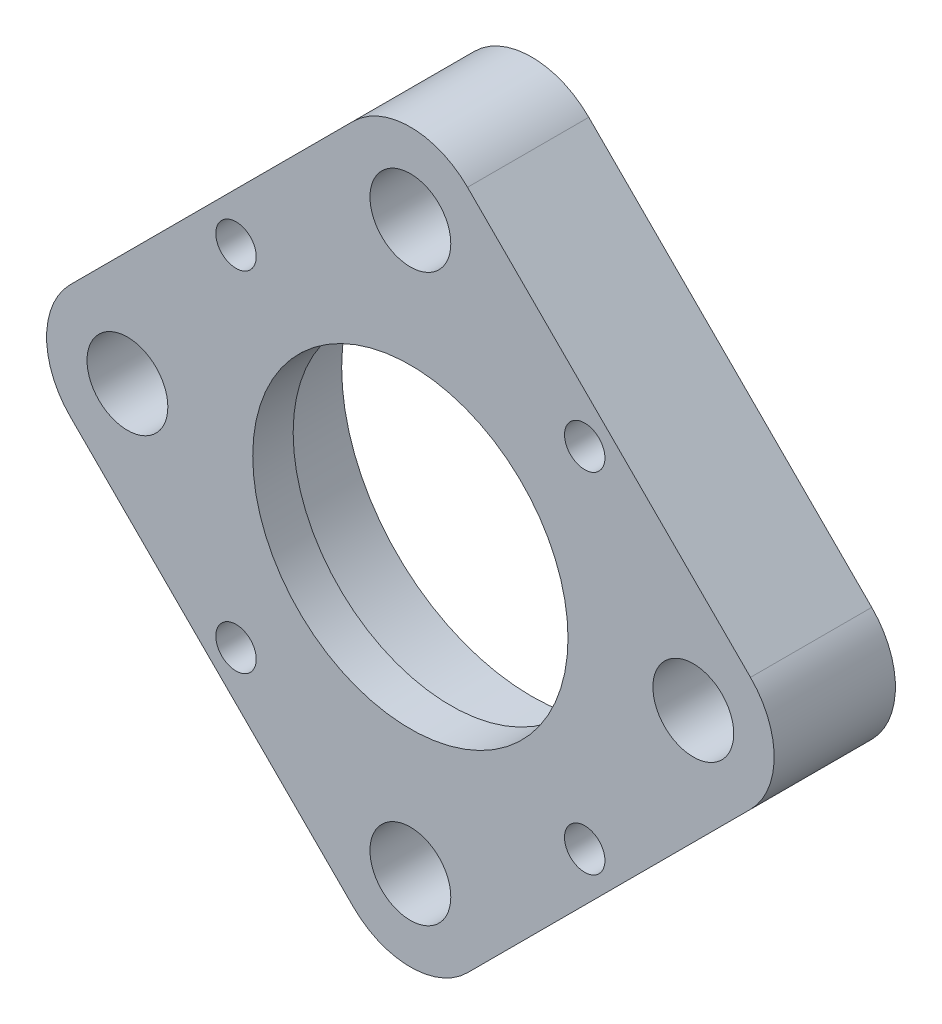
SolidWorks part; units mm, degrees
material "Stop 1060"
ref_plane "Płaszczyzna przednia" through (0, 0, 0) normal (0, 0, 1) x (1, 0, 0)
ref_plane "Płaszczyzna górna" through (0, 0, 0) normal (0, 1, 0) x (1, 0, 0)
ref_plane "Płaszczyzna prawa" through (0, 0, 0) normal (1, 0, 0) x (0, 0, -1)
sketch "Szkic1" plane through (0, 0, 0) normal (0, 0, 1) x (1, 0, 0)
  circle A0 centre (0, 0) radius 23.5
  circle A1 centre (0, 0) radius 19.5
  circle A2 centre (0, 0) radius 35
  dimension "D1" = 39
  dimension "D2" = 47
extrude "Dodanie-wyciągnięcie3" add sketch "Szkic1" along normal blind 5 contours A2 A0 | A0 A1 region at (-22.8353, 0, 0) region at (-34.0101, 0, 0)
sketch "Szkic4" plane through (0, 0, 0) normal (0, 0, -1) x (-1, 0, 0)
  circle A0 centre (0, 0) radius 23.5
  circle A1 centre (0, 0) radius 35
  circle M2 centre (0, 0) radius 35
  dimension "D1" = 47
extrude "Dodanie-wyciągnięcie5" add sketch "Szkic4" along normal blind 10 contours A0 M2 region at (34.0101, 0, 0)
sketch "Szkic10" plane through (0, 0, -10) normal (0, 0, -1) x (-1, 0, 0)
  circle A0 centre (0, 0) radius 30.5
  point P5 (-30.5, 0)
  point P6 (30.5, 0)
sketch "Szkic13" plane through (0, 0, -10) normal (0, 0, -1) x (-1, 0, 0)
  circle A0 centre (0, 35) radius 6
  circle A1 centre (0, 35) radius 10
  circle A3 centre (0, 0) radius 35
  circle A4 centre (0, -35) radius 6
  circle A5 centre (0, -35) radius 10
  circle A6 centre (-35, 0) radius 10
  circle A7 centre (35, 0) radius 10
  point P18 (-35, 0)
  point P20 (35, 0)
  circle M7 centre (0, 0) radius 35
  dimension "D2" = 35
  dimension "D1" = 20
  dimension "D3" = 20
  dimension "D7" = 20
  dimension "D8" = 20
  dimension "D4" = 35
  dimension "D5" = 35
  dimension "D6" = 70
extrude "Dodanie-wyciągnięcie6" add sketch "Szkic13" against normal blind 15 contours A1 M7 | A1 A0 | A5 A4 | A5 M7 | A3 A6 | A3 A7 region at (0, 37.4516, -10) region at (0.2673, 41.2246, -10) region at (38.9765, 0, -10) region at (-38.9765, 0, -10) region at (8.0032, -34.3093, -10) region at (0, -37.4516, -10)
sketch "Szkic16" plane through (0, 0, 5) normal (0, 0, 1) x (1, 0, 0)
  point P0 (0, -35)
  point P1 (0, 35)
  dimension "D1" = 70
hole_wizard "Otwory ustalające Ø10.0mm1" positions "Szkic17" profile "Szkic18" hole size "Ø10.0" standard "ISO" end condition through all
sketch "Szkic17" plane through (0, 0, 5) normal (0, 0, 1) x (1, 0, 0)
  point P0 (0, 35)
  point P3 (0, -35)
  point P7 (-35, 0)
  point P9 (35, 0)
  dimension "D1" = 35
  dimension "D2" = 70
sketch "Szkic18" plane through (0, 35, 5) normal (1, 0, 0) x (0, -1, 0)
  line L0 (0, 0) -> (0, 15)
  line L1 (0, 15) -> (5, 15)
  line L2 (5, 15) -> (5, 0)
  line L5 (5, 0) -> (0, 0)
  line L11 (0, -6.35) -> (0, 107.95) construction
  dimension "Średnica otworu na wylot" = 10
  dimension "Głębokość otworu na wylot" = 15
sketch "Szkic20" plane through (0, 0, 5) normal (0, 0, 1) x (1, 0, 0)
  line L0 (0, 0) -> (-21.5668, 21.5668)
  circle A0 centre (0, 0) radius 30.5
  point P4 (21.5668, 21.5668)
  point P5 (-21.5668, 21.5668)
  point P6 (21.5668, -21.5668)
  point P7 (-21.5668, -21.5668)
  dimension "D1" = 61
hole_wizard "Otwory ustalające Ø5.0mm3" positions "Szkic25" profile "Szkic26" hole size "Ø5.0" standard "ISO" end condition through all
sketch "Szkic25" plane through (0, 0, 5) normal (0, 0, 1) x (1, 0, 0)
  point P0 (-21.5668, 21.5668)
  point P3 (21.5668, 21.5668)
  point P6 (21.5668, -21.5668)
  point P9 (-21.5668, -21.5668)
sketch "Szkic26" plane through (-21.5668, 21.5668, 5) normal (1, 0, 0) x (0, -1, 0)
  line L0 (0, 0) -> (0, 15)
  line L1 (0, 15) -> (2.5, 15)
  line L2 (2.5, 15) -> (2.5, 0)
  line L5 (2.5, 0) -> (0, 0)
  line L11 (0, -6.35) -> (0, 107.95) construction
  dimension "Średnica otworu na wylot" = 5
  dimension "Głębokość otworu na wylot" = 15
fillet "Zaokrąglenie1" [suppressed] radius 360
sketch "Szkic27" plane through (0, 0, -10) normal (0, 0, -1) x (-1, 0, 0)
  line L0 (42.0711, -7.0711) -> (7.0711, -42.0711)
  line L1 (-7.0711, -42.0711) -> (-42.0711, -7.0711)
  line L2 (-42.0711, 7.0711) -> (-7.0711, 42.0711)
  line L3 (7.0711, 42.0711) -> (42.0711, 7.0711)
  line L4 (21.5668, 24.0668) -> (4.6384, 36.867)
  line L5 (-3.9414, 31.9234) -> (-19.4113, 22.8333)
  line L6 (-22.9036, 19.4542) -> (-32.481, 4.3191)
  line L7 (32.481, 4.3191) -> (22.9036, 19.4542)
  line L8 (32.481, -4.3191) -> (21.5668, -19.0668)
  line L9 (22.2032, -23.9844) -> (-1.2729, -30.1648)
  line L10 (-1.2729, -30.1648) -> (-19.2648, -22.542)
  line L11 (-32.481, -4.3191) -> (-22.9036, -19.4542)
  arc A0 (33.5714, -9.8974) -> (33.5714, 9.8974) centre (35, 0) ccw construction
  arc A1 (-9.8974, -33.5714) -> (9.8974, -33.5714) centre (0, -35) ccw construction
  arc A2 (-33.5714, 9.8974) -> (-33.5714, -9.8974) centre (-35, 0) ccw construction
  arc A3 (9.8974, 33.5714) -> (-9.8974, 33.5714) centre (0, 35) ccw construction
  arc A4 (42.0711, 7.0711) -> (42.0711, -7.0711) centre (35, 0) cw
  arc A5 (-7.0711, -42.0711) -> (7.0711, -42.0711) centre (0, -35) ccw
  arc A6 (-7.0711, 42.0711) -> (7.0711, 42.0711) centre (0, 35) cw
  arc A7 (-42.0711, -7.0711) -> (-42.0711, 7.0711) centre (-35, 0) cw
  circle A10 centre (35, 0) radius 5
  circle A11 centre (21.5668, 21.5668) radius 2.5
  circle A12 centre (21.5668, -21.5668) radius 2.5
  circle A13 centre (0, -35) radius 5
  circle A14 centre (-21.5668, -21.5668) radius 2.5
  circle A15 centre (-35, 0) radius 5
  circle A16 centre (-21.5668, 21.5668) radius 2.5
  circle A17 centre (0, 35) radius 5
  arc M19 (-9.8974, 33.5714) -> (-33.5714, 9.8974) centre (0, 0) ccw
  arc M20 (-33.5714, 9.8974) -> (-33.5714, -9.8974) centre (-35, 0) ccw
  arc M21 (-33.5714, -9.8974) -> (-9.8974, -33.5714) centre (0, 0) ccw
  arc M22 (-9.8974, -33.5714) -> (9.8974, -33.5714) centre (0, -35) ccw
  arc M23 (9.8974, -33.5714) -> (33.5714, -9.8974) centre (0, 0) ccw
  arc M24 (33.5714, -9.8974) -> (33.5714, 9.8974) centre (35, 0) ccw
  arc M25 (33.5714, 9.8974) -> (9.8974, 33.5714) centre (0, 0) ccw
  arc M26 (9.8974, 33.5714) -> (-9.8974, 33.5714) centre (0, 35) ccw
  dimension "D1" = 10
  dimension "D2" = 10
  dimension "D3" = 10
  dimension "D4" = 10
extrude "Dodanie-wyciągnięcie7" add sketch "Szkic27" against normal blind 15 contours L3 M25 M24 | L3 M26 M25 | L2 M19 M26 | L2 M20 M19 | L1 M21 M20 | L1 M22 M21 | L0 M23 M22 | L0 M24 M23 region at (-34.2937, -13.1603, -10) region at (-34.2937, 13.1603, -10) region at (-13.1603, -34.2937, -10) region at (-13.1603, 34.2937, -10) region at (13.1603, -34.2937, -10) region at (13.1603, 34.2937, -10) region at (34.2937, -13.1603, -10) region at (34.2937, 13.1603, -10)
sketch "Szkic28" plane through (0, 0, -10) normal (0, 0, -1) x (-1, 0, 0)
  line L0 (42.0711, -7.0711) -> (0, -49.1421)
  line L1 (0, -49.1421) -> (-49.1421, 0)
  line L2 (-49.1421, 0) -> (0, 49.1421)
  line L3 (0, 49.1421) -> (49.1421, 0)
  line L4 (49.1421, 0) -> (41.0704, -8.0718)
  circle A0 centre (0, 0) radius 52.5094
  line M2 (42.0711, 7.0711) -> (27.5312, 21.6109)
  arc M3 (27.5312, 21.6109) -> (21.6109, 27.5312) centre (0, 0) ccw
  line M4 (21.6109, 27.5312) -> (7.0711, 42.0711)
  line M6 (-7.0711, 42.0711) -> (-21.6109, 27.5312)
  arc M7 (-21.6109, 27.5312) -> (-27.5312, 21.6109) centre (0, 0) ccw
  line M8 (-27.5312, 21.6109) -> (-42.0711, 7.0711)
  line M10 (-42.0711, -7.0711) -> (-27.5312, -21.6109)
  arc M11 (-27.5312, -21.6109) -> (-21.6109, -27.5312) centre (0, 0) ccw
  line M12 (-21.6109, -27.5312) -> (-7.0711, -42.0711)
  line M14 (7.0711, -42.0711) -> (21.6109, -27.5312)
  arc M15 (21.6109, -27.5312) -> (27.5312, -21.6109) centre (0, 0) ccw
  line M16 (27.5312, -21.6109) -> (42.0711, -7.0711)
extrude "Wytnij-wyciągnięcie6" cut sketch "Szkic28" against normal blind 15 contours A0 L3 L4 L0 L1 L2 M16 M15 M14 M12 M11 M10 M8 M7 M6 M4 M3 M2 | L0 M15 | L1 M11 | L2 M7 | L3 M3 region at (-24.6422, -24.6422, -10) region at (-24.6422, 24.6422, -10) region at (24.6422, -24.6422, -10) region at (24.6422, 24.6422, -10) region at (51.0242, 0, -10)
